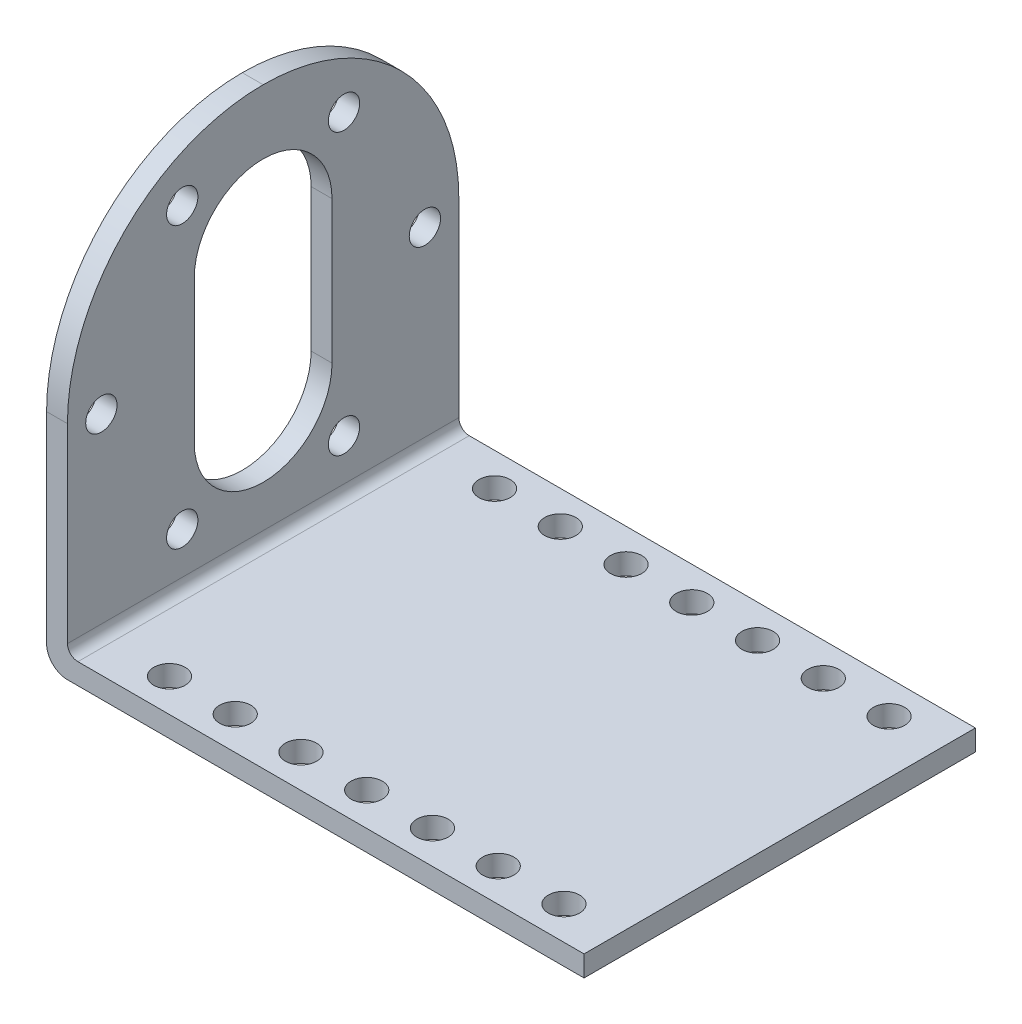
SolidWorks part; units mm, degrees
ref_plane "Front Plane" through (0, 0, 0) normal (0, 0, 1) x (1, 0, 0)
ref_plane "Top Plane" through (0, 0, 0) normal (0, 1, 0) x (1, 0, 0)
ref_plane "Right Plane" through (0, 0, 0) normal (1, 0, 0) x (0, 0, -1)
sketch "Sketch1" plane through (0, 0, 0) normal (0, 1, 0) x (1, 0, 0)
  line L1 (-25.75, -18.75) -> (25.75, -18.75)
  line L2 (-25.75, -18.75) -> (-25.75, 18.75)
  line L3 (-25.75, 18.75) -> (25.75, 18.75)
  line L4 (25.75, -18.75) -> (25.75, 18.75)
  line L5 (-25.75, -18.75) -> (25.75, 18.75) construction
  line L6 (-25.75, 18.75) -> (25.75, -18.75) construction
  point P0 (0, 0)
  dimension "D1" = 37.5
  dimension "D2" = 51.5
extrude "Boss-Extrude1" add sketch "Sketch1" along normal blind 40
sketch "Sketch2" plane through (0, 0, 18.75) normal (0, 0, 1) x (1, 0, 0)
  line L0 (-25.75, 0) -> (25.75, 0) construction
  line L1 (-23.75, 2) -> (25.75, 2)
  line L2 (-23.75, 2) -> (-23.75, 40)
  line L3 (-23.75, 40) -> (25.75, 40)
  line L4 (25.75, 2) -> (25.75, 40)
  line L5 (-25.75, 40) -> (-25.75, 0) construction
  dimension "D1" = 2
  dimension "D2" = 2
extrude "Cut-Extrude1" cut sketch "Sketch2" against normal through all
fillet "Fillet1" radius 1 1 edges at (-23.75, 2, 0)
fillet "Fillet2" radius 2 1 edges at (-25.75, 0, 0)
sketch "Sketch3" plane through (0, 2, 0) normal (0, 1, 0) x (1, 0, 0)
  line L0 (-10.85, -15.575) -> (-10.85, 15.575) construction
  line L1 (-17.15, -15.575) -> (-17.15, 15.575) construction
  line L2 (-4.55, -15.575) -> (-4.55, 15.575) construction
  line L3 (1.75, -15.575) -> (1.75, 15.575) construction
  line L4 (8.05, -15.575) -> (8.05, 15.575) construction
  line L5 (14.35, -15.575) -> (14.35, 15.575) construction
  line L6 (20.65, -15.575) -> (20.65, 15.575) construction
  line L7 (-25.75, 18.75) -> (-25.75, -18.75) construction
  point P2 (-17.15, 0)
  dimension "D1" = 31.15
  dimension "D2" = 7
  dimension "D3" = 8.6
hole_wizard "Ø3.0mm Dowel Hole1" positions "Sketch6" profile "Sketch5" hole size "Ø3.0" standard "ANSI Metric" end condition through all
sketch "Sketch6" plane through (0, 2, 0) normal (0, 1, 0) x (1, 0, 0)
  point P0 (-17.15, -15.575)
  point P3 (-17.15, 15.575)
  point P6 (-10.85, -15.575)
  point P9 (-4.55, -15.575)
  point P12 (1.75, -15.575)
  point P15 (8.05, -15.575)
  point P18 (14.35, -15.575)
  point P21 (20.65, -15.575)
  point P24 (20.65, 15.575)
  point P27 (14.35, 15.575)
  point P30 (8.05, 15.575)
  point P33 (1.75, 15.575)
  point P36 (-4.55, 15.575)
  point P39 (-10.85, 15.575)
sketch "Sketch5" plane through (-17.15, 2, 15.575) normal (1, 0, 0) x (0, 0, 1)
  line L0 (0, 0) -> (0, 2)
  line L1 (0, 2) -> (1.5, 2)
  line L2 (1.5, 2) -> (1.5, 0)
  line L5 (1.5, 0) -> (0, 0)
  line L11 (0, -6.35) -> (0, 107.95) construction
  dimension "Thru Hole Dia." = 3
  dimension "Thru Hole Depth" = 2
sketch "Sketch7" plane through (-25.75, 0, 0) normal (-1, 0, 0) x (0, 0, 1)
  line L0 (18.75, 0) -> (-18.75, 0) construction
  line L1 (15.5, 20.4234) -> (7.75, 33.8468) construction
  line L2 (7.75, 33.8468) -> (-7.75, 33.8468) construction
  line L3 (-7.75, 33.8468) -> (-15.5, 20.4234) construction
  line L4 (-15.5, 20.4234) -> (-7.75, 7) construction
  line L5 (-7.75, 7) -> (7.75, 7) construction
  line L6 (7.75, 7) -> (15.5, 20.4234) construction
  line L7 (0, 27.2468) -> (0, 13.6) construction
  line L8 (6.6, 27.2468) -> (6.6, 13.6)
  line L9 (-6.6, 27.2468) -> (-6.6, 13.6)
  circle A0 centre (0, 20.4234) radius 13.4234 construction
  arc A1 (6.6, 27.2468) -> (-6.6, 27.2468) centre (0, 27.2468) ccw
  arc A2 (-6.6, 13.6) -> (6.6, 13.6) centre (0, 13.6) ccw
  point P1 (0, 20.4234)
  point P11 (0, 0)
  point P19 (0, 33.8468)
  point P20 (0, 33.8468)
  point P21 (0, 15.5883)
  point P22 (0, 20.5164)
  point P23 (0, 7)
  point P24 (0, 7)
  dimension "D1" = 31
  dimension "D2" = 7
  dimension "D3" = 13.2
extrude "Cut-Extrude2" cut sketch "Sketch7" against normal blind 10
fillet "Fillet3" radius 18.75 2 edges at (-24.75, 40, 18.75) (-24.75, 40, -18.75)
hole_wizard "Ø3.0mm Dowel Hole2" positions "Sketch8" profile "Sketch9" hole size "Ø3.0" standard "ANSI Metric" end condition through all
sketch "Sketch8" plane through (-25.75, 0, 0) normal (-1, 0, 0) x (0, 0, 1)
  point P0 (-7.75, 33.8468)
  point P3 (7.75, 33.8468)
  point P6 (15.5, 20.4234)
  point P9 (7.75, 7)
  point P12 (-7.75, 7)
  point P15 (-15.5, 20.4234)
sketch "Sketch9" plane through (-25.75, 33.8468, -7.75) normal (0, 1, 0) x (0, 0, 1)
  line L0 (0, 0) -> (0, 51.5)
  line L1 (0, 51.5) -> (1.5, 51.5)
  line L2 (1.5, 51.5) -> (1.5, 0)
  line L5 (1.5, 0) -> (0, 0)
  line L11 (0, -6.35) -> (0, 107.95) construction
  dimension "Thru Hole Dia." = 3
  dimension "Thru Hole Depth" = 51.5
